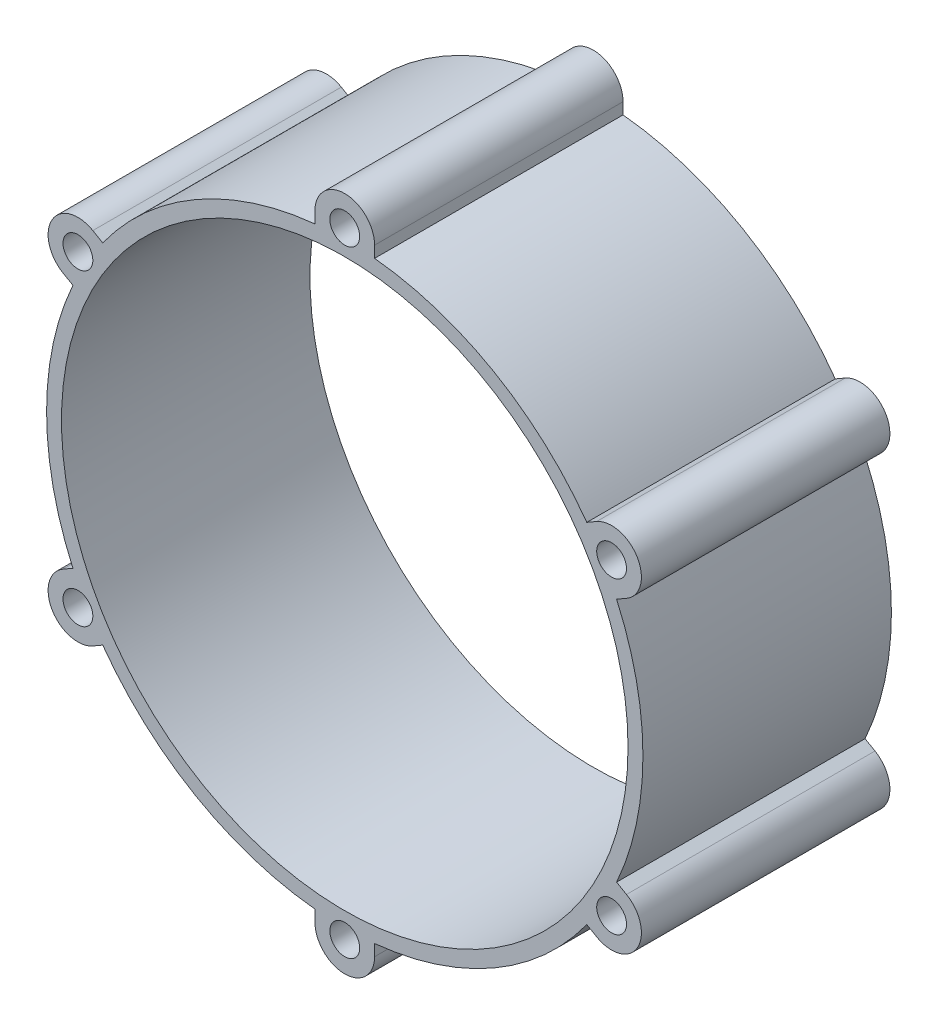
SolidWorks part; units mm, degrees
ref_plane "Front Plane" through (0, 0, 0) normal (0, 0, 1) x (1, 0, 0)
ref_plane "Top Plane" through (0, 0, 0) normal (0, 1, 0) x (1, 0, 0)
ref_plane "Right Plane" through (0, 0, 0) normal (1, 0, 0) x (0, 0, -1)
sketch "Sketch1" plane through (0, 0, 0) normal (0, 0, 1) x (1, 0, 0)
  line L0 (6, 62) -> (6, 59.6992)
  line L1 (-6, 62) -> (-6, 59.6992)
  line L2 (56.6936, 25.8038) -> (54.7011, 24.6535)
  line L3 (50.6936, 36.1962) -> (48.7011, 35.0458)
  line L4 (50.6936, -36.1962) -> (48.7011, -35.0458)
  line L5 (56.6936, -25.8038) -> (54.7011, -24.6535)
  line L6 (-6, -62) -> (-6, -59.6992)
  line L7 (6, -62) -> (6, -59.6992)
  line L8 (-56.6936, -25.8038) -> (-54.7011, -24.6535)
  line L9 (-50.6936, -36.1962) -> (-48.7011, -35.0458)
  line L10 (-50.6936, 36.1962) -> (-48.7011, 35.0458)
  line L11 (-56.6936, 25.8038) -> (-54.7011, 24.6535)
  line L12 (0, 0) -> (6, 59.6992) construction
  circle A0 centre (0, 0) radius 60
  circle A1 centre (0, 0) radius 57
  arc A2 (6, 62) -> (-6, 62) centre (0, 62) ccw
  arc A3 (56.6936, 25.8038) -> (50.6936, 36.1962) centre (53.6936, 31) ccw
  arc A4 (50.6936, -36.1962) -> (56.6936, -25.8038) centre (53.6936, -31) ccw
  arc A5 (-6, -62) -> (6, -62) centre (0, -62) ccw
  arc A6 (-56.6936, -25.8038) -> (-50.6936, -36.1962) centre (-53.6936, -31) ccw
  arc A7 (-50.6936, 36.1962) -> (-56.6936, 25.8038) centre (-53.6936, 31) ccw
  dimension "D1" = 120
  dimension "D2" = 6
  dimension "D4" = 3
  dimension "D3" = 62
  dimension "D5" = 6
extrude "Boss-Extrude1" add sketch "Sketch1" along normal mid plane 50 contours L0 A2 L1 A0 | L10 A7 L11 A0 | L8 A6 L9 A0 | L6 A5 L7 A0 | L4 A4 L5 A0 | L2 A3 L3 A0 | A1 | A0 region at (0, 63.4372, 0) region at (54.9382, 31.7186, 0) region at (-54.9382, 31.7186, 0) region at (54.9382, -31.7186, 0) region at (-54.9382, -31.7186, 0) region at (0, -63.4372, 0) region at (0, 0, 0)
sketch "Sketch3" plane through (0, 0, -25) normal (0, 0, -1) x (-1, 0, 0)
  circle A0 centre (0, 62) radius 3
  dimension "D1" = 6
extrude "Cut-Extrude1" cut sketch "Sketch3" against normal through all
pattern_circular "CirPattern1" count 6 over 360 about axis through (0, 0, -25) along (0, 0, 1) of "Cut-Extrude1"
